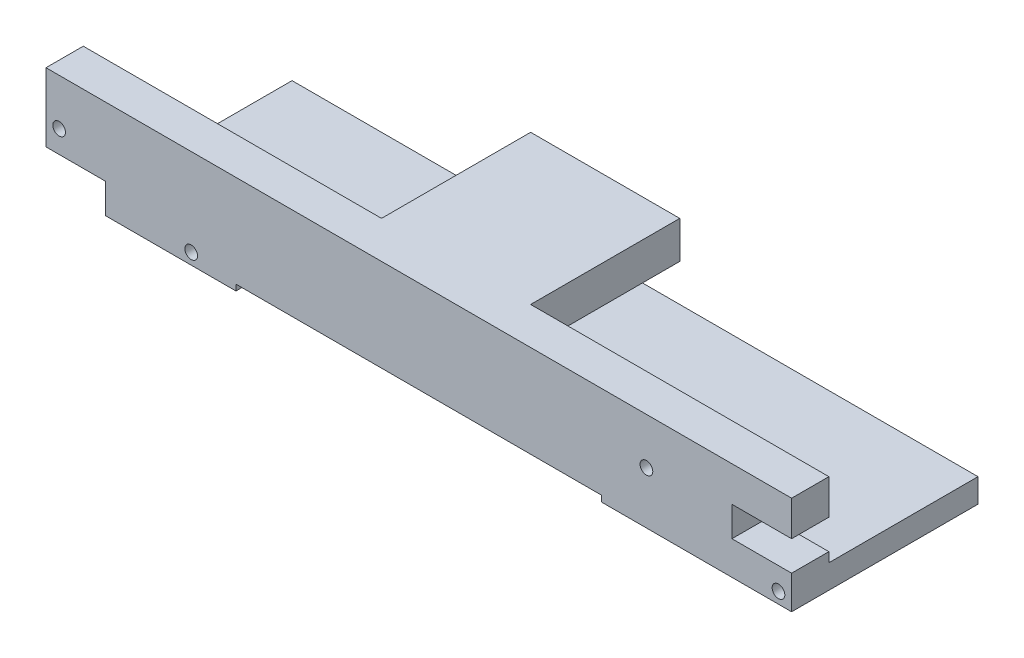
SolidWorks part; units mm, degrees
ref_plane "Front Plane" through (0, 0, 0) normal (0, 0, 1) x (1, 0, 0)
ref_plane "Top Plane" through (0, 0, 0) normal (0, 1, 0) x (1, 0, 0)
ref_plane "Right Plane" through (0, 0, 0) normal (1, 0, 0) x (0, 0, -1)
sketch "Sketch1" plane through (0, 0, 0) normal (0, 1, 0) x (1, 0, 0)
  line L1 (-63.5, -15.875) -> (63.5, -15.875)
  line L2 (-63.5, -15.875) -> (-63.5, 15.875)
  line L3 (-63.5, 15.875) -> (63.5, 15.875)
  line L4 (63.5, -15.875) -> (63.5, 15.875)
  line L5 (-63.5, -15.875) -> (63.5, 15.875) construction
  line L6 (-63.5, 15.875) -> (63.5, -15.875) construction
  point P0 (0, 0)
  dimension "D1" = 31.75
  dimension "D2" = 127
extrude "Boss-Extrude1" add sketch "Sketch1" along normal blind 16.764
sketch "Sketch2" plane through (-63.5, 0, 0) normal (-1, 0, 0) x (0, 0, 1)
  line L0 (-15.875, 16.764) -> (-15.875, 0) construction
  line L1 (-15.875, 10.414) -> (9.525, 10.414)
  line L2 (-15.875, 10.414) -> (-15.875, 4.064)
  line L3 (-15.875, 4.064) -> (9.525, 4.064)
  line L4 (9.525, 10.414) -> (9.525, 4.064)
  point P7 (0, 0)
  point P9 (0, 0)
  point P10 (-15.875, 6.9561)
  point P11 (0, 0)
  dimension "D1" = 6.35
  dimension "D2" = 25.4
  dimension "D3" = 4.064
extrude "Cut-Extrude1" cut sketch "Sketch2" against normal up to surface (127 mm away) up to face at (63.5, 8.382, 0)
sketch "Sketch3" plane through (-63.5, 0, 0) normal (-1, 0, 0) x (0, 0, 1)
  line L0 (9.525, 10.414) -> (-15.875, 10.414) construction
  line L1 (-15.875, 16.764) -> (9.525, 16.764)
  line L2 (-15.875, 16.764) -> (-15.875, 10.414)
  line L3 (-15.875, 10.414) -> (9.525, 10.414)
  line L4 (9.525, 16.764) -> (9.525, 10.414)
  dimension "D1" = 25.4
extrude "Cut-Extrude2" cut sketch "Sketch3" against normal blind 50.8
mirror "Mirror1" about plane through (0, 0, 0) normal (1, 0, 0) of "Cut-Extrude2"
sketch "Sketch5" plane through (0, 0, 0) normal (0, -1, 0) x (1, 0, 0)
  line L0 (-27.9908, 3.175) -> (27.9908, 3.175) construction
  line L1 (-63.5, 15.875) -> (63.5, 15.875) construction
  line L3 (-31.1468, 15.875) -> (31.1468, 15.875)
  line L4 (-31.1468, 15.875) -> (-31.1468, -1.2446)
  line L5 (-31.1468, -1.2446) -> (31.1468, -1.2446)
  line L6 (31.1468, 15.875) -> (31.1468, -1.2446)
  circle A0 centre (-27.9908, 3.175) radius 1.0732
  circle A1 centre (27.9908, 3.175) radius 1.0732
  point P0 (-27.9908, 3.175)
  point P1 (27.9908, 3.175)
  point P2 (0, 3.175)
  point P12 (0, -1.2446)
  point P14 (0, 0)
  point P18 (0, -1.2446)
  line M3 (63.5, 15.875) -> (-63.5, 15.875)
  dimension "D5" = 2.1463
  dimension "D6" = 2.1463
  dimension "D1" = 12.7
  dimension "D2" = 55.9816
  dimension "D3" = 17.1196
  dimension "D4" = 62.2935
extrude "Cut-Extrude3" cut sketch "Sketch5" against normal blind 1.016 contours L6 L4 L5 A0 A1 M3 | A0 | A1 region at (0, 0, 7.3435) region at (-27.9908, 0, 3.175) region at (27.9908, 0, 3.175)
extrude "Cut-Extrude4" cut sketch "Sketch5<3>" against normal through all contours A0 | A1 region at (-27.9908, 0, 3.175) region at (27.9908, 0, 3.175)
sketch "Sketch5<3>" plane through (0, 0, 0) normal (0, -1, 0) x (1, 0, 0) same geometry as "Sketch5"
sketch "Sketch6" plane through (0, 0, 15.875) normal (0, 0, 1) x (1, 0, 0)
  line L0 (-63.5, 0) -> (-31.1468, 0) construction
  line L1 (-63.5, 10.7823) -> (-36.5379, 10.7823)
  line L2 (-63.5, 10.7823) -> (-63.5, 0)
  line L3 (-63.5, 0) -> (-36.5379, 0)
  line L4 (-36.5379, 10.7823) -> (-36.5379, 0)
  line L5 (-61.2648, 8.8773) -> (-38.7731, 8.8773) construction
  line L6 (-61.2648, 8.8773) -> (-61.2648, 1.905) construction
  line L7 (-61.2648, 1.905) -> (-38.7731, 1.905) construction
  line L8 (-38.7731, 8.8773) -> (-38.7731, 1.905) construction
  line L9 (-63.5, 16.764) -> (-63.5, 0) construction
  line L10 (36.5379, 10.7823) -> (63.5, 10.7823)
  line L11 (-36.5379, 10.7823) -> (-46.6979, 10.7823)
  line L12 (-36.5379, 10.7823) -> (-36.5379, 5.7023)
  line L13 (-36.5379, 5.7023) -> (-46.6979, 5.7023)
  line L14 (-46.6979, 10.7823) -> (-46.6979, 5.7023)
  line L15 (-63.5, 0) -> (-53.34, 0)
  line L16 (-63.5, 0) -> (-63.5, 5.08)
  line L17 (-63.5, 5.08) -> (-53.34, 5.08)
  line L18 (-53.34, 0) -> (-53.34, 5.08)
  line L19 (36.5379, 10.7823) -> (36.5379, 0)
  line L20 (36.5379, 0) -> (63.5, 0)
  line L21 (63.5, 10.7823) -> (63.5, 0)
  line L22 (38.7731, 8.8773) -> (61.2648, 8.8773) construction
  line L23 (38.7731, 8.8773) -> (38.7731, 1.905) construction
  line L24 (38.7731, 1.905) -> (61.2648, 1.905) construction
  line L25 (61.2648, 8.8773) -> (61.2648, 1.905) construction
  line L26 (63.5, 10.7823) -> (53.34, 10.7823)
  line L27 (63.5, 10.7823) -> (63.5, 5.7023)
  line L28 (63.5, 5.7023) -> (53.34, 5.7023)
  line L29 (53.34, 10.7823) -> (53.34, 5.7023)
  line L30 (36.5379, 0) -> (46.6979, 0)
  line L31 (36.5379, 0) -> (36.5379, 5.08)
  line L32 (36.5379, 5.08) -> (46.6979, 5.08)
  line L33 (46.6979, 0) -> (46.6979, 5.08)
  line L34 (31.1468, 0) -> (63.5, 0) construction
  line L35 (63.5, 16.764) -> (63.5, 0) construction
  circle A0 centre (-61.2648, 8.8773) radius 1.0795
  circle A1 centre (-38.7731, 8.8773) radius 1.0795
  circle A2 centre (-38.7731, 1.905) radius 1.0795
  circle A3 centre (-61.2648, 1.905) radius 1.0795
  circle A4 centre (38.7731, 8.8773) radius 1.0795
  circle A5 centre (61.2648, 8.8773) radius 1.0795
  circle A6 centre (61.2648, 1.905) radius 1.0795
  circle A7 centre (38.7731, 1.905) radius 1.0795
  point P42 (0, 0)
  line M14 (-63.5, 0) -> (-31.1468, 0)
  dimension "D7" = 2.159
  dimension "D8" = 2.159
  dimension "D9" = 2.159
  dimension "D10" = 2.159
  dimension "D21" = 2.159
  dimension "D22" = 2.159
  dimension "D23" = 2.159
  dimension "D24" = 2.159
  dimension "D1" = 26.9621
  dimension "D2" = 10.7823
  dimension "D3" = 2.2352
  dimension "D4" = 2.2352
  dimension "D5" = 1.905
  dimension "D6" = 1.905
  dimension "D11" = 10.16
  dimension "D12" = 5.08
  dimension "D13" = 10.16
  dimension "D14" = 5.08
  dimension "D15" = 26.9621
  dimension "D16" = 10.7823
  dimension "D17" = 2.2352
  dimension "D18" = 2.2352
  dimension "D19" = 1.905
  dimension "D20" = 1.905
  dimension "D25" = 10.16
  dimension "D26" = 5.08
  dimension "D27" = 10.16
  dimension "D28" = 5.08
extrude "Cut-Extrude8" cut sketch "Sketch6" against normal up to surface (31.75 mm away) contours A5 | L10 L29 L28 L21 A5 | A4 | A6 | L18 L17 L2 A3 M14 | A3 | A2 | A0 region at (-58.2028, 2.5885, 15.875) region at (58.2028, 8.1938, 15.875) region at (-61.2648, 8.8773, 15.875) region at (-38.7731, 1.905, 15.875) region at (-61.2648, 1.905, 15.875) region at (38.7731, 8.8773, 15.875) region at (61.2648, 8.8773, 15.875) region at (61.2648, 1.905, 15.875) up to face at (0, 2.032, -15.875)
